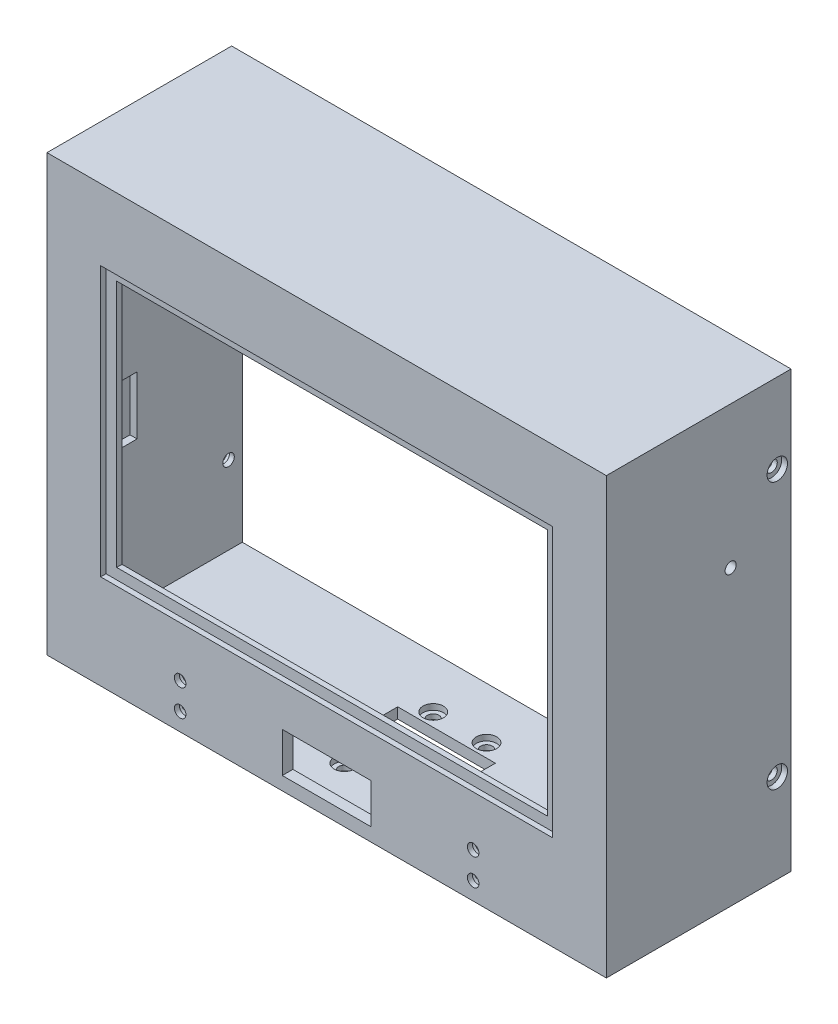
SolidWorks part; units mm, degrees
ref_plane "Front Plane" through (0, 0, 0) normal (0, 0, 1) x (1, 0, 0)
ref_plane "Top Plane" through (0, 0, 0) normal (0, 1, 0) x (1, 0, 0)
ref_plane "Right Plane" through (0, 0, 0) normal (1, 0, 0) x (0, 0, -1)
sketch "Sketch1" plane through (0, 0, 0) normal (0, 0, 1) x (1, 0, 0)
  line L1 (-63, 60) -> (63, 60)
  line L2 (-63, 60) -> (-63, 158)
  line L3 (-63, 158) -> (63, 158)
  line L4 (63, 60) -> (63, 158)
extrude "Boss-Extrude1" add sketch "Sketch1" along normal blind 41.6 from offset 38.4
sketch "Sketch2" plane through (0, 0, 0) normal (0, 0, 1) x (1, 0, 0)
  line L1 (-60.6, 62.4) -> (60.6, 62.4)
  line L2 (-60.6, 62.4) -> (-60.6, 155.6)
  line L3 (-60.6, 155.6) -> (60.6, 155.6)
  line L4 (60.6, 62.4) -> (60.6, 155.6)
extrude "Boss-Extrude2" add sketch "Sketch2" along normal blind 41.6 from offset 36 separate body
combine bodies "Combine1" operation type subtract main body 101 bodies to subtract 102
sketch "Sketch3" plane through (0, 0, 0) normal (0, 0, 1) x (1, 0, 0)
  line L1 (-48.5, 83.74) -> (48.5, 83.74)
  line L2 (-48.5, 83.74) -> (-48.5, 139.6)
  line L3 (-48.5, 139.6) -> (48.5, 139.6)
  line L4 (48.5, 83.74) -> (48.5, 139.6)
extrude "Boss-Extrude3" add sketch "Sketch3" along normal blind 4.4 from offset 76.6 separate body
combine bodies "Combine2" operation type subtract main body 103 bodies to subtract 104
sketch "Sketch4" plane through (0, 0, 0) normal (0, 0, 1) x (1, 0, 0)
  line L1 (-50.9, 81.3) -> (50.9, 81.3)
  line L2 (-50.9, 81.3) -> (-50.9, 142)
  line L3 (-50.9, 142) -> (50.9, 142)
  line L4 (50.9, 81.3) -> (50.9, 142)
extrude "Boss-Extrude4" add sketch "Sketch4" along normal blind 2.2 from offset 78.8 separate body
combine bodies "Combine3" operation type subtract main body 105 bodies to subtract 106
sketch "Sketch5" plane through (0, 0, 0) normal (0, 0, 1) x (1, 0, 0)
  circle A0 centre (-56.3, 78.45) radius 2.8
extrude "Boss-Extrude5" add sketch "Sketch5" along normal blind 4.5 from offset 73.1
sketch "Sketch6" plane through (0, 0, 0) normal (0, 0, 1) x (1, 0, 0)
  circle A0 centre (-56.3, 78.45) radius 1
extrude "Boss-Extrude6" add sketch "Sketch6" along normal blind 7.1 from offset 72.1 separate body
combine bodies "Combine4" operation type subtract main body 108 bodies to subtract 109
sketch "Sketch7" plane through (0, 0, 0) normal (0, 0, 1) x (1, 0, 0)
  circle A0 centre (-56.3, 140.55) radius 2.8
extrude "Boss-Extrude7" add sketch "Sketch7" along normal blind 4.5 from offset 73.1
sketch "Sketch8" plane through (0, 0, 0) normal (0, 0, 1) x (1, 0, 0)
  circle A0 centre (-56.3, 140.55) radius 1
extrude "Boss-Extrude8" add sketch "Sketch8" along normal blind 7.1 from offset 72.1 separate body
combine bodies "Combine5" operation type subtract main body 111 bodies to subtract 112
sketch "Sketch9" plane through (0, 0, 0) normal (0, 0, 1) x (1, 0, 0)
  circle A0 centre (56.3, 78.45) radius 2.8
extrude "Boss-Extrude9" add sketch "Sketch9" along normal blind 4.5 from offset 73.1
sketch "Sketch10" plane through (0, 0, 0) normal (0, 0, 1) x (1, 0, 0)
  circle A0 centre (56.3, 78.45) radius 1
extrude "Boss-Extrude10" add sketch "Sketch10" along normal blind 7.1 from offset 72.1 separate body
combine bodies "Combine6" operation type subtract main body 114 bodies to subtract 115
sketch "Sketch11" plane through (0, 0, 0) normal (0, 0, 1) x (1, 0, 0)
  circle A0 centre (56.3, 140.55) radius 2.8
extrude "Boss-Extrude11" add sketch "Sketch11" along normal blind 4.5 from offset 73.1
sketch "Sketch12" plane through (0, 0, 0) normal (0, 0, 1) x (1, 0, 0)
  circle A0 centre (56.3, 140.55) radius 1
extrude "Boss-Extrude12" add sketch "Sketch12" along normal blind 7.1 from offset 72.1 separate body
combine bodies "Combine7" operation type subtract main body 117 bodies to subtract 118
sketch "Sketch13" plane through (0, 0, 0) normal (0, 0, 1) x (1, 0, 0)
  line L1 (-64, 107.5) -> (-60.1, 107.5)
  line L2 (-64, 107.5) -> (-64, 121.5)
  line L3 (-64, 121.5) -> (-60.1, 121.5)
  line L4 (-60.1, 107.5) -> (-60.1, 121.5)
extrude "Boss-Extrude13" add sketch "Sketch13" along normal blind 8 from offset 65.9 separate body
combine bodies "Combine8" operation type subtract main body 119 bodies to subtract 120
sketch "Sketch14" plane through (0, 0, 0) normal (0, 0, 1) x (1, 0, 0)
  line L1 (-62.2, 94.4) -> (-60.1, 94.4)
  line L2 (-62.2, 94.4) -> (-62.2, 107.5)
  line L3 (-62.2, 107.5) -> (-60.1, 107.5)
  line L4 (-60.1, 94.4) -> (-60.1, 107.5)
extrude "Boss-Extrude14" add sketch "Sketch14" along normal blind 12 from offset 62.1 separate body
combine bodies "Combine9" operation type subtract main body 121 bodies to subtract 122
sketch "Sketch15" plane through (0, 0, 0) normal (1, 0, 0) x (0, 0, -1)
  circle A0 centre (-52, 126) radius 8.3
extrude "Boss-Extrude15" add sketch "Sketch15" along normal blind 1.2 from offset 60.6 offset against normal yes
sketch "Sketch16" plane through (0, 0, 0) normal (1, 0, 0) x (0, 0, -1)
  circle A0 centre (-52, 126) radius 7.3
extrude "Boss-Extrude16" add sketch "Sketch16" along normal blind 1.3 from offset 60.6 separate body offset against normal yes
combine bodies "Combine10" operation type subtract main body 124 bodies to subtract 125
sketch "Sketch17" plane through (0, 0, 0) normal (1, 0, 0) x (0, 0, -1)
  circle A0 centre (-52, 126) radius 1.25
extrude "Boss-Extrude17" add sketch "Sketch17" along normal blind 4.4 from offset 64 separate body offset against normal yes
combine bodies "Combine11" operation type subtract main body 126 bodies to subtract 127
sketch "Sketch18" plane through (0, 0, 0) normal (1, 0, 0) x (0, 0, -1)
  circle A0 centre (-41.5, 80) radius 1.3
extrude "Boss-Extrude18" add sketch "Sketch18" along normal blind 4.4 from offset 64 separate body offset against normal yes
combine bodies "Combine12" operation type subtract main body 128 bodies to subtract 129
sketch "Sketch19" plane through (0, 0, 0) normal (1, 0, 0) x (0, 0, -1)
  circle A0 centre (-41.5, 80) radius 2.3
extrude "Boss-Extrude19" add sketch "Sketch19" along normal blind 2.3 from offset 64 separate body offset against normal yes
combine bodies "Combine13" operation type subtract main body 130 bodies to subtract 131
sketch "Sketch20" plane through (0, 0, 0) normal (1, 0, 0) x (0, 0, -1)
  circle A0 centre (-41.5, 140) radius 1.3
extrude "Boss-Extrude20" add sketch "Sketch20" along normal blind 4.4 from offset 64 separate body offset against normal yes
combine bodies "Combine14" operation type subtract main body 132 bodies to subtract 133
sketch "Sketch21" plane through (0, 0, 0) normal (1, 0, 0) x (0, 0, -1)
  circle A0 centre (-41.5, 140) radius 2.3
extrude "Boss-Extrude21" add sketch "Sketch21" along normal blind 2.3 from offset 64 separate body offset against normal yes
combine bodies "Combine15" operation type subtract main body 134 bodies to subtract 135
sketch "Sketch22" plane through (0, 0, 0) normal (1, 0, 0) x (0, 0, -1)
  circle A0 centre (-52, 126) radius 8.3
extrude "Boss-Extrude22" add sketch "Sketch22" along normal blind 1.2 from offset 59.4
sketch "Sketch23" plane through (0, 0, 0) normal (1, 0, 0) x (0, 0, -1)
  circle A0 centre (-52, 126) radius 7.3
extrude "Boss-Extrude23" add sketch "Sketch23" along normal blind 1.3 from offset 59.3 separate body
combine bodies "Combine16" operation type subtract main body 137 bodies to subtract 138
sketch "Sketch24" plane through (0, 0, 0) normal (1, 0, 0) x (0, 0, -1)
  circle A0 centre (-52, 126) radius 1.25
extrude "Boss-Extrude24" add sketch "Sketch24" along normal blind 4.4 from offset 59.6 separate body
combine bodies "Combine17" operation type subtract main body 139 bodies to subtract 140
sketch "Sketch25" plane through (0, 0, 0) normal (1, 0, 0) x (0, 0, -1)
  circle A0 centre (-41.5, 80) radius 1.3
extrude "Boss-Extrude25" add sketch "Sketch25" along normal blind 4.4 from offset 59.6 separate body
combine bodies "Combine18" operation type subtract main body 141 bodies to subtract 142
sketch "Sketch26" plane through (0, 0, 0) normal (1, 0, 0) x (0, 0, -1)
  circle A0 centre (-41.5, 80) radius 2.3
extrude "Boss-Extrude26" add sketch "Sketch26" along normal blind 2.3 from offset 61.7 separate body
combine bodies "Combine19" operation type subtract main body 143 bodies to subtract 144
sketch "Sketch27" plane through (0, 0, 0) normal (1, 0, 0) x (0, 0, -1)
  circle A0 centre (-41.5, 140) radius 1.3
extrude "Boss-Extrude27" add sketch "Sketch27" along normal blind 4.4 from offset 59.6 separate body
combine bodies "Combine20" operation type subtract main body 145 bodies to subtract 146
sketch "Sketch28" plane through (0, 0, 0) normal (1, 0, 0) x (0, 0, -1)
  circle A0 centre (-41.5, 140) radius 2.3
extrude "Boss-Extrude28" add sketch "Sketch28" along normal blind 2.3 from offset 61.7 separate body
combine bodies "Combine21" operation type subtract main body 147 bodies to subtract 148
sketch "Sketch29" plane through (0, 0, 0) normal (0, 0, 1) x (1, 0, 0)
  line L1 (-11, 59) -> (11, 59)
  line L2 (-11, 59) -> (-11, 63.4)
  line L3 (-11, 63.4) -> (11, 63.4)
  line L4 (11, 59) -> (11, 63.4)
extrude "Boss-Extrude29" add sketch "Sketch29" along normal blind 14 from offset 53 separate body
combine bodies "Combine22" operation type subtract main body 149 bodies to subtract 150
sketch "Sketch30" plane through (0, 0, 0) normal (0, 1, 0) x (1, 0, 0)
  circle A0 centre (-6, -50) radius 1.3
extrude "Boss-Extrude30" add sketch "Sketch30" along normal blind 4.4 from offset 59 separate body
combine bodies "Combine23" operation type subtract main body 151 bodies to subtract 152
sketch "Sketch31" plane through (0, 0, 0) normal (0, 1, 0) x (1, 0, 0)
  circle A0 centre (-6, -50) radius 2.3
extrude "Boss-Extrude31" add sketch "Sketch31" along normal blind 1.8 from offset 61.1 separate body
combine bodies "Combine24" operation type subtract main body 153 bodies to subtract 154
sketch "Sketch32" plane through (0, 0, 0) normal (0, 1, 0) x (1, 0, 0)
  circle A0 centre (-6, -70) radius 1.3
extrude "Boss-Extrude32" add sketch "Sketch32" along normal blind 4.4 from offset 59 separate body
combine bodies "Combine25" operation type subtract main body 155 bodies to subtract 156
sketch "Sketch33" plane through (0, 0, 0) normal (0, 1, 0) x (1, 0, 0)
  circle A0 centre (-6, -70) radius 2.3
extrude "Boss-Extrude33" add sketch "Sketch33" along normal blind 1.8 from offset 61.1 separate body
combine bodies "Combine26" operation type subtract main body 157 bodies to subtract 158
sketch "Sketch34" plane through (0, 0, 0) normal (0, 1, 0) x (1, 0, 0)
  circle A0 centre (6, -50) radius 1.3
extrude "Boss-Extrude34" add sketch "Sketch34" along normal blind 4.4 from offset 59 separate body
combine bodies "Combine27" operation type subtract main body 159 bodies to subtract 160
sketch "Sketch35" plane through (0, 0, 0) normal (0, 1, 0) x (1, 0, 0)
  circle A0 centre (6, -50) radius 2.3
extrude "Boss-Extrude35" add sketch "Sketch35" along normal blind 1.8 from offset 61.1 separate body
combine bodies "Combine28" operation type subtract main body 161 bodies to subtract 162
sketch "Sketch36" plane through (0, 0, 0) normal (0, 1, 0) x (1, 0, 0)
  circle A0 centre (6, -70) radius 1.3
extrude "Boss-Extrude36" add sketch "Sketch36" along normal blind 4.4 from offset 59 separate body
combine bodies "Combine29" operation type subtract main body 163 bodies to subtract 164
sketch "Sketch37" plane through (0, 0, 0) normal (0, 1, 0) x (1, 0, 0)
  circle A0 centre (6, -70) radius 2.3
extrude "Boss-Extrude37" add sketch "Sketch37" along normal blind 1.8 from offset 61.1 separate body
combine bodies "Combine30" operation type subtract main body 165 bodies to subtract 166
sketch "Sketch38" plane through (0, 0, 0) normal (0, 0, 1) x (1, 0, 0)
  line L1 (-10, 63) -> (10, 63)
  line L2 (-10, 63) -> (-10, 72)
  line L3 (-10, 72) -> (10, 72)
  line L4 (10, 63) -> (10, 72)
extrude "Boss-Extrude38" add sketch "Sketch38" along normal blind 4.4 from offset 76.6 separate body
combine bodies "Combine31" operation type subtract main body 167 bodies to subtract 168
sketch "Sketch39" plane through (0, 0, 0) normal (0, 0, 1) x (1, 0, 0)
  circle A0 centre (-33, 64) radius 1.3
extrude "Boss-Extrude39" add sketch "Sketch39" along normal blind 4.4 from offset 76.6 separate body
combine bodies "Combine32" operation type subtract main body 169 bodies to subtract 170
sketch "Sketch40" plane through (0, 0, 0) normal (0, 0, 1) x (1, 0, 0)
  circle A0 centre (-33, 64) radius 2.3
extrude "Boss-Extrude40" add sketch "Sketch40" along normal blind 1.8 from offset 77.1 separate body
combine bodies "Combine33" operation type subtract main body 171 bodies to subtract 172
sketch "Sketch41" plane through (0, 0, 0) normal (0, 0, 1) x (1, 0, 0)
  circle A0 centre (-33, 70) radius 1.3
extrude "Boss-Extrude41" add sketch "Sketch41" along normal blind 4.4 from offset 76.6 separate body
combine bodies "Combine34" operation type subtract main body 173 bodies to subtract 174
sketch "Sketch42" plane through (0, 0, 0) normal (0, 0, 1) x (1, 0, 0)
  circle A0 centre (-33, 70) radius 2.3
extrude "Boss-Extrude42" add sketch "Sketch42" along normal blind 1.8 from offset 77.1 separate body
combine bodies "Combine35" operation type subtract main body 175 bodies to subtract 176
sketch "Sketch43" plane through (0, 0, 0) normal (0, 0, 1) x (1, 0, 0)
  circle A0 centre (33, 64) radius 1.3
extrude "Boss-Extrude43" add sketch "Sketch43" along normal blind 4.4 from offset 76.6 separate body
combine bodies "Combine36" operation type subtract main body 177 bodies to subtract 178
sketch "Sketch44" plane through (0, 0, 0) normal (0, 0, 1) x (1, 0, 0)
  circle A0 centre (33, 64) radius 2.3
extrude "Boss-Extrude44" add sketch "Sketch44" along normal blind 1.8 from offset 77.1 separate body
combine bodies "Combine37" operation type subtract main body 179 bodies to subtract 180
sketch "Sketch45" plane through (0, 0, 0) normal (0, 0, 1) x (1, 0, 0)
  circle A0 centre (33, 70) radius 1.3
extrude "Boss-Extrude45" add sketch "Sketch45" along normal blind 4.4 from offset 76.6 separate body
combine bodies "Combine38" operation type subtract main body 181 bodies to subtract 182
sketch "Sketch46" plane through (0, 0, 0) normal (0, 0, 1) x (1, 0, 0)
  circle A0 centre (33, 70) radius 2.3
extrude "Boss-Extrude46" add sketch "Sketch46" along normal blind 1.8 from offset 77.1 separate body
combine bodies "Combine39" operation type subtract main body 183 bodies to subtract 184
sketch "Sketch47" plane through (0, 0, 0) normal (0, 1, 0) x (1, 0, 0)
  circle A0 centre (0, -46) radius 2.8
extrude "Boss-Extrude47" add sketch "Sketch47" along normal blind 3 from offset 152.6
sketch "Sketch48" plane through (0, 0, 0) normal (0, 1, 0) x (1, 0, 0)
  circle A0 centre (0, -46) radius 1
extrude "Boss-Extrude48" add sketch "Sketch48" along normal blind 5.1 from offset 152.1 separate body
combine bodies "Combine40" operation type subtract main body 186 bodies to subtract 187
